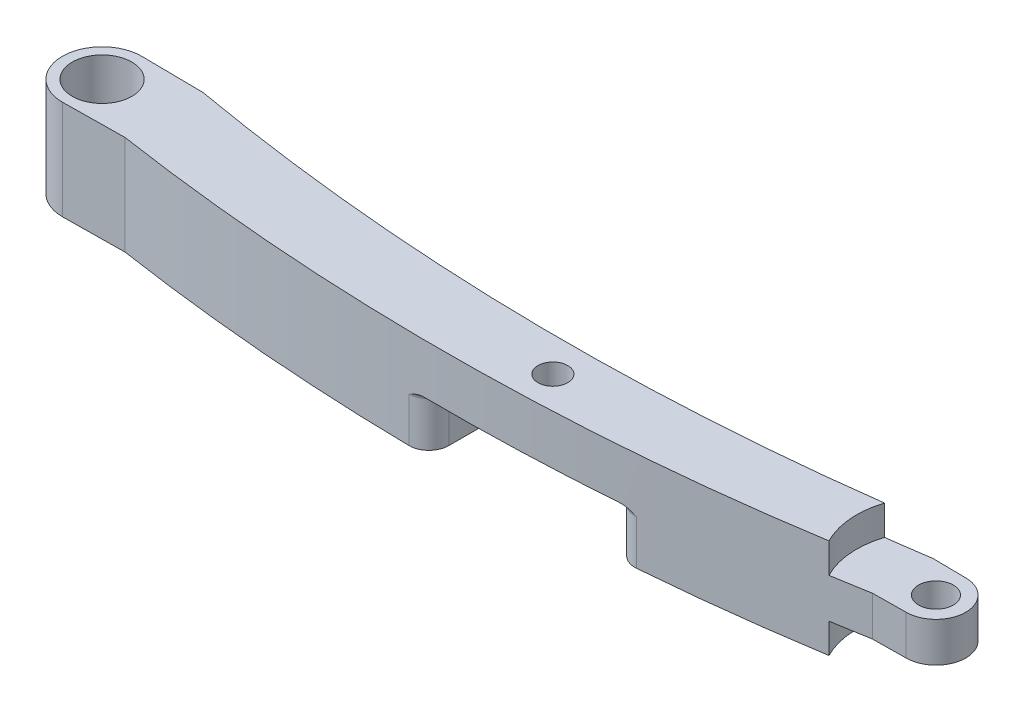
SolidWorks part; units mm, degrees
ref_plane "Front Plane" through (0, 0, 0) normal (0, 0, 1) x (1, 0, 0)
ref_plane "Top Plane" through (0, 0, 0) normal (0, 1, 0) x (1, 0, 0)
ref_plane "Right Plane" through (0, 0, 0) normal (1, 0, 0) x (0, 0, -1)
sketch "Sketch1" plane through (0, 0, 0) normal (0, 1, 0) x (1, 0, 0)
  line L0 (-15.9656, 0) -> (68.0344, 0) construction
  line L1 (-15.9656, 4) -> (-9.73, 3.9258)
  line L2 (-15.9656, -4) -> (-9.73, -3.9258)
  line L3 (64.6619, -3.0401) -> (68.0344, -3)
  line L4 (64.6619, 3.0401) -> (68.0344, 3)
  circle A0 centre (-15.9656, 0) radius 3
  circle A1 centre (68.0344, 0) radius 1.75
  arc A2 (-15.9656, 4) -> (-15.9656, -4) centre (-15.9656, 0) ccw
  arc A4 (68.0344, -3) -> (68.0344, 3) centre (68.0344, 0) ccw
  arc A5 (64.6619, 3.0401) -> (-9.73, 3.9258) centre (30.1678, 230.4388) cw
  arc A6 (-9.73, -3.9258) -> (64.6619, -3.0401) centre (24.7641, 223.4729) ccw
  dimension "D1" = 6
  dimension "D2" = 3.5
  dimension "D6" = 230
  dimension "D7" = 230
  dimension "D3" = 4
  dimension "D4" = 3
  dimension "D5" = 84
extrude "Boss-Extrude1" add sketch "Sketch1" along normal mid plane 10 contours A0 A1 A4 L1 A2 L2 region at (24.5503, 0, 1.7774)
ref_plane "Plane1" through (68.0344, 0, 0) normal (1, 0, 0) x (0, 0, -1)
sketch "Sketch3" plane through (68.0344, 0, 0) normal (1, 0, 0) x (0, 0, -1)
  line L0 (0, 5) -> (0, -5) construction
  line L1 (8, -5) -> (0, -5)
  line L2 (8, -5) -> (8, -2)
  line L3 (8, -2) -> (0, -2)
  line L4 (0, -5) -> (0, -2)
  line L5 (8, -5) -> (0, -2) construction
  line L6 (8, -2) -> (0, -5) construction
  line L7 (-3, -5) -> (3, -5) construction
  line L9 (0, 6.0105) -> (8, 6.0105)
  line L10 (0, 6.0105) -> (0, 2)
  line L11 (0, 2) -> (8, 2)
  line L12 (8, 6.0105) -> (8, 2)
  line L13 (0, 6.0105) -> (8, 2) construction
  line L14 (0, 2) -> (8, 6.0105) construction
  line L15 (3, 5) -> (-3, 5) construction
  point P0 (4, -3.5)
  point P9 (0, -5)
  point P10 (4, 4.0052)
  dimension "D1" = 8
  dimension "D2" = 3
  dimension "D3" = 8
  dimension "D4" = 3
revolve "Cut-Revolve1" cut sketch "Sketch3" angle 360 about L10
sketch "Sketch4" plane through (0, 5, 0) normal (0, 1, 0) x (1, 0, 0)
  circle A0 centre (32.4668, -3.0228) radius 1.5
  dimension "D1" = 3
extrude "Cut-Extrude1" cut sketch "Sketch4" against normal blind 10
sketch "Sketch7" plane through (0, 0, 0) normal (0, 0, 1) x (1, 0, 0)
  line L0 (-9.73, -5) -> (60.9242, -5) construction
  line L1 (23.4668, 0) -> (41.4668, 0)
  line L2 (23.4668, 0) -> (23.4668, -5)
  line L3 (23.4668, -5) -> (41.4668, -5)
  line L4 (41.4668, 0) -> (41.4668, -5)
  line L6 (32.4668, -5) -> (32.4668, 5) construction
  point P8 (32.4668, 0)
  dimension "D1" = 5
  dimension "D2" = 0
  dimension "D3" = 18
extrude "Cut-Extrude3" cut sketch "Sketch7" against normal through all both and the other way through all
fillet "Fillet2" radius 2 4 edges at (23.4668, -2.5, -0.5365) (41.4668, -2.5, -0.7165) (41.4668, -2.5, 5.9198) (23.4668, -2.5, 6.5234)
fillet "Fillet3" radius 0.5 6 edges at (42.1118, 0, 5.2298) (41.4668, 0, 2.4692) (22.8707, 0, 5.9276) (23.4668, 0, 2.9506) (42.0126, 0, -0.1934) (22.9073, 0, 0.0105)
